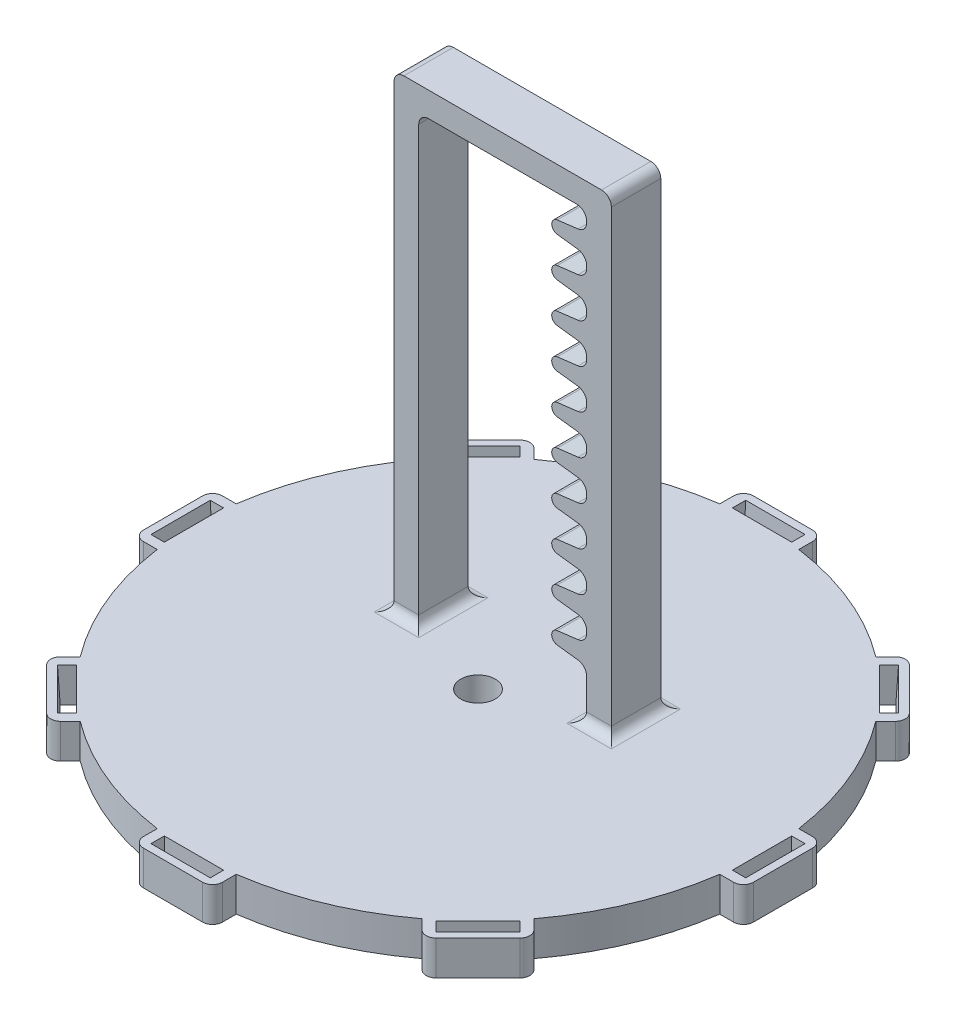
SolidWorks part; units mm, degrees
ref_plane "Front Plane" through (0, 0, 0) normal (0, 0, 1) x (1, 0, 0)
ref_plane "Top Plane" through (0, 0, 0) normal (0, 1, 0) x (1, 0, 0)
ref_plane "Right Plane" through (0, 0, 0) normal (1, 0, 0) x (0, 0, -1)
sketch "Sketch1" plane through (0, 0, 0) normal (0, 1, 0) x (1, 0, 0)
  line L0 (-8, 56.9408) -> (-8, 59.7408)
  line L1 (0, 57.5) -> (0, -57.5) construction
  line L2 (8, 56.9408) -> (8, 59.7408)
  line L3 (-6, 61.7408) -> (6, 61.7408)
  line L4 (39.4147, 47.8999) -> (47.8999, 39.4147)
  line L9 (34.6063, 45.9201) -> (36.5862, 47.8999)
  line L10 (45.9201, 34.6063) -> (47.8999, 36.5862)
  line L15 (61.7408, 6) -> (61.7408, -6)
  line L16 (56.9408, 8) -> (59.7408, 8)
  line L17 (56.9408, -8) -> (59.7408, -8)
  line L22 (47.8999, -39.4147) -> (39.4147, -47.8999)
  line L23 (45.9201, -34.6063) -> (47.8999, -36.5862)
  line L24 (34.6063, -45.9201) -> (36.5862, -47.8999)
  line L29 (6, -61.7408) -> (-6, -61.7408)
  line L30 (8, -56.9408) -> (8, -59.7408)
  line L31 (-8, -56.9408) -> (-8, -59.7408)
  line L36 (-39.4147, -47.8999) -> (-47.8999, -39.4147)
  line L37 (-34.6063, -45.9201) -> (-36.5862, -47.8999)
  line L38 (-45.9201, -34.6063) -> (-47.8999, -36.5862)
  line L43 (-61.7408, -6) -> (-61.7408, 6)
  line L44 (-56.9408, -8) -> (-59.7408, -8)
  line L45 (-56.9408, 8) -> (-59.7408, 8)
  line L50 (-47.8999, 39.4147) -> (-39.4147, 47.8999)
  line L51 (-45.9201, 34.6063) -> (-47.8999, 36.5862)
  line L52 (-34.6063, 45.9201) -> (-36.5862, 47.8999)
  arc A0 (-8, 56.9408) -> (-34.6063, 45.9201) centre (0, 0) ccw
  arc A1 (6, 61.7408) -> (8, 59.7408) centre (6, 59.7408) cw
  arc A2 (-6, 61.7408) -> (-8, 59.7408) centre (-6, 59.7408) ccw
  arc A3 (39.4147, 47.8999) -> (36.5862, 47.8999) centre (38.0005, 46.4857) ccw
  arc A4 (47.8999, 39.4147) -> (47.8999, 36.5862) centre (46.4857, 38.0005) cw
  arc A5 (61.7408, 6) -> (59.7408, 8) centre (59.7408, 6) ccw
  arc A6 (61.7408, -6) -> (59.7408, -8) centre (59.7408, -6) cw
  arc A7 (47.8999, -39.4147) -> (47.8999, -36.5862) centre (46.4857, -38.0005) ccw
  arc A8 (39.4147, -47.8999) -> (36.5862, -47.8999) centre (38.0005, -46.4857) cw
  arc A9 (6, -61.7408) -> (8, -59.7408) centre (6, -59.7408) ccw
  arc A10 (-6, -61.7408) -> (-8, -59.7408) centre (-6, -59.7408) cw
  arc A11 (-39.4147, -47.8999) -> (-36.5862, -47.8999) centre (-38.0005, -46.4857) ccw
  arc A12 (-47.8999, -39.4147) -> (-47.8999, -36.5862) centre (-46.4857, -38.0005) cw
  arc A13 (-61.7408, -6) -> (-59.7408, -8) centre (-59.7408, -6) ccw
  arc A14 (-61.7408, 6) -> (-59.7408, 8) centre (-59.7408, 6) cw
  arc A15 (-47.8999, 39.4147) -> (-47.8999, 36.5862) centre (-46.4857, 38.0005) ccw
  arc A16 (-39.4147, 47.8999) -> (-36.5862, 47.8999) centre (-38.0005, 46.4857) cw
  arc A17 (-45.9201, 34.6063) -> (-56.9408, 8) centre (0, 0) ccw
  arc A18 (-56.9408, -8) -> (-45.9201, -34.6063) centre (0, 0) ccw
  arc A19 (34.6063, 45.9201) -> (8, 56.9408) centre (0, 0) ccw
  arc A20 (-34.6063, -45.9201) -> (-8, -56.9408) centre (0, 0) ccw
  arc A21 (8, -56.9408) -> (34.6063, -45.9201) centre (0, 0) ccw
  arc A22 (45.9201, -34.6063) -> (56.9408, -8) centre (0, 0) ccw
  arc A23 (56.9408, 8) -> (45.9201, 34.6063) centre (0, 0) ccw
  point P11 (8, 61.7408)
  point P14 (-8, 61.7408)
  point P17 (-8, 58.3408)
  point P98 (0, 0)
  dimension "D1" = 115
  dimension "D2" = 2
  dimension "D3" = 16
  dimension "D4" = 2.8
  dimension "D7" = 8
extrude "Boss-Extrude1" add sketch "Sketch1" along normal blind 7
sketch "Sketch2" plane through (0, 7, 0) normal (0, 1, 0) x (1, 0, 0)
  line L0 (-57.5, 0) -> (57.5, 0) construction
  line L1 (0, 0) -> (0, 10) construction
  line L7 (17, 5) -> (22, 5)
  line L14 (0, 10) -> (29.7122, 10) construction
  line L15 (0, 10) -> (-19.5, 10) construction
  line L17 (17, 5) -> (17, 15)
  line L18 (-22, 15) -> (-17, 15)
  line L19 (-22, 15) -> (-22, 5)
  line L20 (-22, 5) -> (-17, 5)
  line L21 (-17, 15) -> (-17, 5)
  line L22 (-22, 15) -> (-17, 5) construction
  line L23 (-22, 5) -> (-17, 15) construction
  line L24 (17, 15) -> (22, 15)
  line L25 (22, 5) -> (22, 15)
  line L26 (17, 5) -> (22, 15) construction
  line L27 (17, 15) -> (22, 5) construction
  circle A0 centre (0, 0) radius 57.5 construction
  point P8 (19.5, 10)
  dimension "D1" = 10
  dimension "D2" = 17
  dimension "D3" = 17
  dimension "D4" = 10
  dimension "D5" = 5
  dimension "D6" = 10
  dimension "D7" = 5
extrude "Boss-Extrude2" add sketch "Sketch2" along normal blind 95
sketch "Sketch15" plane through (0, 0, 0) normal (0, -1, 0) x (1, 0, 0)
  circle A0 centre (0, 0) radius 3.5
  dimension "D1" = 7
extrude "Cut-Extrude3" cut sketch "Sketch15" along direction (0, 1, 0) on the side against the normal up to surface (7 mm away) contours A0 up to face at (0, 7, 0)
sketch "Sketch16" plane through (0, 0, 0) normal (0, -1, 0) x (1, 0, 0)
  line L1 (-6, 59.8) -> (6, 59.8)
  line L2 (-6, 59.8) -> (-6, 57.5)
  line L3 (-6, 57.5) -> (6, 57.5)
  line L4 (6, 59.8) -> (6, 57.5)
  point P5 (0, 57.5)
  dimension "D1" = 2.3
  dimension "D2" = 12
  dimension "D3" = 57.5
sketch "Sketch17" plane through (0, 7, 0) normal (0, 1, 0) x (1, 0, 0)
  line L0 (-6, -57.5) -> (6, -57.5) construction
  line L1 (-6, -57.5) -> (6, -57.5)
  line L2 (-6, -57.5) -> (-6, -60.2)
  line L3 (-6, -60.2) -> (6, -60.2)
  line L4 (6, -60.2) -> (6, -57.5)
  dimension "D1" = 2.7
ref_axis "Axis1" through (0, 107.1, 0) along (0, -1, 0)
loft "Cut-Loft2" cut profiles "Sketch16", "Sketch17"
pattern_circular "CirPattern1" count 8 over 360 about axis through (0, 107.1, 0) along (0, -1, 0) of "Cut-Loft2"
sketch "Sketch18" plane through (-17, 0, 0) normal (1, 0, 0) x (0, 0, -1)
  line L0 (15, 102) -> (15, 7) construction
  line L1 (5, 102) -> (15, 102)
  line L2 (5, 102) -> (5, 97)
  line L3 (5, 97) -> (15, 97)
  line L4 (15, 102) -> (15, 97)
  dimension "D1" = 5
extrude "Boss-Extrude3" add sketch "Sketch18" along normal up to surface (34 mm away) up to face at (17, 54.5, -10)
sketch "Sketch19" plane through (0, 0, -15) normal (0, 0, -1) x (-1, 0, 0)
  line L0 (-17, 93) -> (-11.0447, 92.2688)
  line L1 (-17, 97) -> (-17, 7) construction
  line L4 (-11, 91) -> (-19.8185, 91) construction
  line L5 (-17, 89) -> (-11.0447, 89.7312)
  line L6 (-17, 93) -> (-17, 89)
  arc A1 (-11.0447, 92.2688) -> (-11.0447, 89.7312) centre (-11.2005, 91) cw
  dimension "D1" = 6
  dimension "D4" = 4
  dimension "D2" = 7
  dimension "D3" = 4
extrude "Boss-Extrude4" add sketch "Sketch19" against normal blind 10
fillet "Fillet1" radius 2 2 edges at (17, 93, -10) (17, 89, -10)
fillet "Fillet2" radius 2 12 edges at (-22, 102, -10) (22, 102, -10) (17, 7, -10) (19.5, 7, -15) (19.5, 7, -5) (22, 7, -10) (-19.5, 7, -5) (-19.5, 7, -15) (-22, 7, -10) (-17, 7, -10) (-17, 97, -10) (17, 97, -10)
pattern_linear "LPattern2" count 10 spacing 8 along (0, -1, 0) of "Fillet1", "Boss-Extrude4"
equation "\"85.00.00mm\"=8500"
